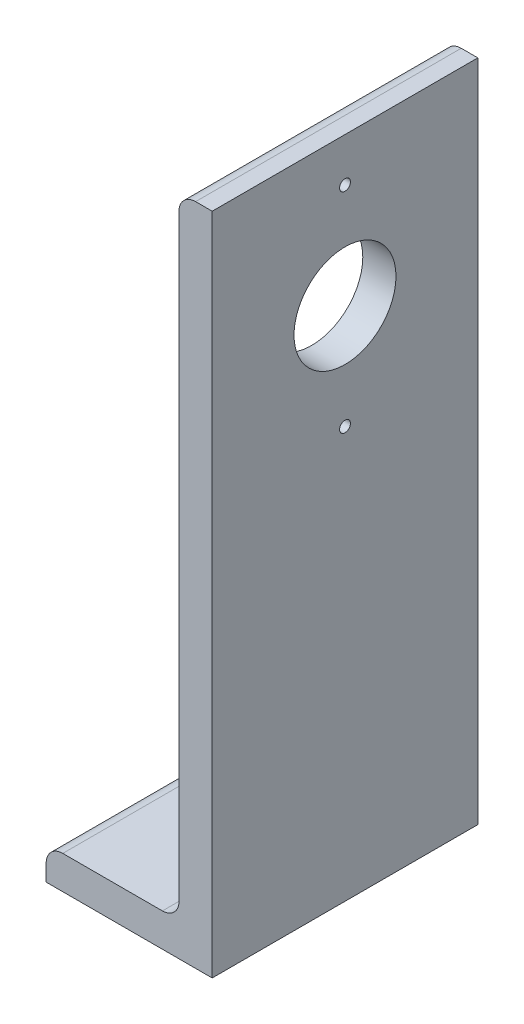
SolidWorks part; units mm, degrees
ref_plane "Front Plane" through (0, 0, 0) normal (0, 0, 1) x (1, 0, 0)
ref_plane "Top Plane" through (0, 0, 0) normal (0, 1, 0) x (1, 0, 0)
ref_plane "Right Plane" through (0, 0, 0) normal (1, 0, 0) x (0, 0, -1)
sketch "Sketch2" plane through (0, 0, 0) normal (0, 0, 1) x (1, 0, 0)
  line L0 (-15.875, 0) -> (15.875, 0)
  line L1 (15.875, 0) -> (15.875, 127)
  line L2 (15.875, 127) -> (9.525, 127) construction
  line L3 (9.525, 123.825) -> (9.525, 9.525)
  line L4 (6.35, 6.35) -> (-12.7, 6.35)
  line L5 (-15.875, 0) -> (-15.875, 6.35) construction
  line L6 (12.7, 127) -> (15.875, 127)
  line L7 (-15.875, 3.175) -> (-15.875, 0)
  arc A0 (9.525, 123.825) -> (12.7, 127) centre (12.7, 123.825) cw
  arc A1 (-15.875, 3.175) -> (-12.7, 6.35) centre (-12.7, 3.175) cw
  arc A2 (9.525, 9.525) -> (6.35, 6.35) centre (6.35, 9.525) cw
  dimension "Vert" = 127
  dimension "Horz" = 31.75
  dimension "Thickness" = 6.35
extrude "Boss-Extrude1" add sketch "Sketch2" along normal mid plane 50.8
ref_plane "Contact Plane 1" through (0, 6.35, 0) normal (0, 1, 0) x (1, 0, 0)
ref_plane "Contact Plane 2" through (9.525, 0, 0) normal (-1, 0, 0) x (0, 0, 1)
sketch "Sketch3" plane through (0, 0, 0) normal (0, -1, 0) x (1, 0, 0)
  line L0 (15.875, 0) -> (-15.875, 0) construction
  line L1 (15.875, 25.4) -> (15.875, -25.4) construction
  line L2 (-15.875, 25.4) -> (-15.875, -25.4) construction
  circle A0 centre (-4.826, 0) radius 4.765
  dimension "D1" = 9.53
  dimension "D2" = 20.701
extrude "Cut-Extrude1" cut sketch "Sketch3" against normal through all contours A0
sketch "Sketch4" plane through (15.875, 0, 0) normal (1, 0, 0) x (0, 0, -1)
  line L0 (-25.4, 0) -> (-25.4, 127) construction
  circle A1 centre (0, 98.65) radius 9.75
  dimension "D1" = 25.4
  dimension "D2" = 19.5
  dimension "D3" = 98.65
extrude "Cut-Extrude2" cut sketch "Sketch4" against normal blind 12.7
sketch "Sketch5" plane through (15.875, 0, 0) normal (1, 0, 0) x (0, 0, -1)
  line L0 (0, 98.65) -> (-32.3063, 98.65) construction
  circle A0 centre (0, 78.65) radius 1.04
  circle A1 centre (0, 118.65) radius 1.04
  dimension "D1" = 2.08
  dimension "D2" = 20
extrude "Cut-Extrude3" cut sketch "Sketch5" against normal blind 10
